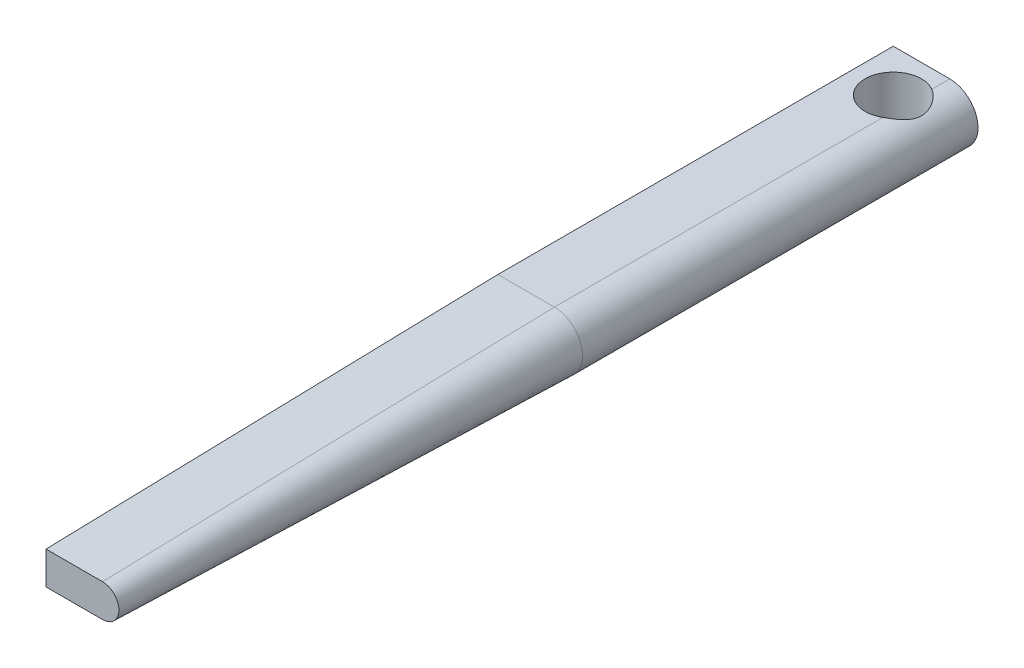
SolidWorks part; units mm, degrees
ref_plane "前视基准面" through (0, 0, 0) normal (0, 0, 1) x (1, 0, 0)
ref_plane "上视基准面" through (0, 0, 0) normal (0, 1, 0) x (1, 0, 0)
ref_plane "右视基准面" through (0, 0, 0) normal (1, 0, 0) x (0, 0, -1)
sketch "草图1" plane through (0, 0, 0) normal (0, 0, 1) x (1, 0, 0)
  line L1 (0, 10) -> (10, 10)
  line L2 (0, 10) -> (0, 0)
  line L3 (0, 0) -> (10, 0)
  arc A0 (10, 10) -> (10, 0) centre (10, 5) cw
  dimension "D1" = 10
extrude "拉伸1" add sketch "草图1" along normal blind 150
sketch "草图2" plane through (0, 10, 0) normal (0, 1, 0) x (1, 0, 0)
  line L0 (0, -150) -> (0, 0) construction
  line L2 (10, 0) -> (0, 0) construction
  circle A0 centre (7.5, -7.5) radius 5
  dimension "D1" = 10
  dimension "D2" = 7.5
  dimension "D3" = 7.5
extrude "拉伸2" cut sketch "草图2" against normal through all
chamfer "倒角1" distance 80 angle 1.5 3 edges at (5, 0, 150) (15, 5, 150) (5, 10, 150) first distance on face at (5.4167, 0, 52.5) first distance on face at (11.8717, 5, 41.25) first distance on face at (5.4167, 10, 52.5)
